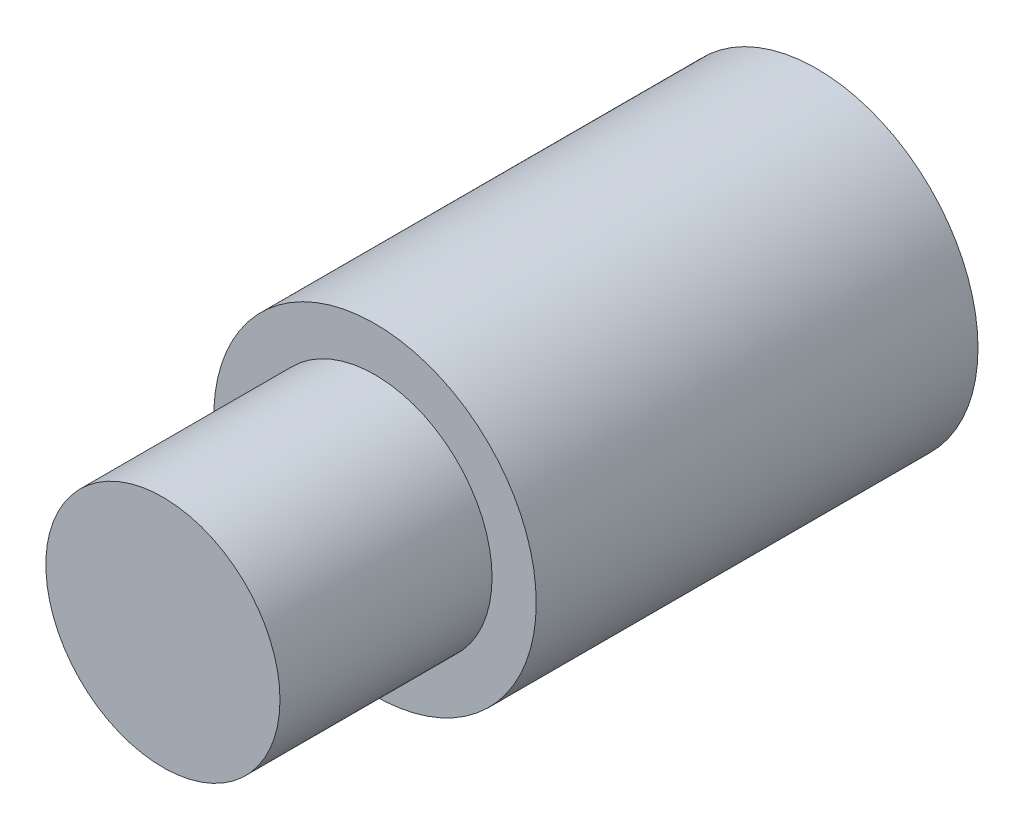
SolidWorks part; units mm, degrees
ref_plane "Front Plane" through (0, 0, 0) normal (0, 0, 1) x (1, 0, 0)
ref_plane "Top Plane" through (0, 0, 0) normal (0, 1, 0) x (1, 0, 0)
ref_plane "Right Plane" through (0, 0, 0) normal (1, 0, 0) x (0, 0, -1)
sketch "Sketch1" plane through (0, 0, 0) normal (0, 0, 1) x (1, 0, 0)
  circle A0 centre (0, 0) radius 3.65
  circle A1 centre (0, 0) radius 2.8
  dimension "D2" = 5.6
  dimension "D1" = 7.3
extrude "Boss-Extrude1" add sketch "Sketch1" along normal blind 9
sketch "Sketch2" plane through (0, 0, 9) normal (0, 0, 1) x (1, 0, 0)
  circle A0 centre (0, 0) radius 3.65 construction
  circle A1 centre (0, 0) radius 3.65
extrude "Boss-Extrude2" add sketch "Sketch2" along normal blind 1
sketch "Sketch3" plane through (0, 0, 10) normal (0, 0, 1) x (1, 0, 0)
  circle A0 centre (0, 0) radius 2.65
  dimension "D1" = 5.3
extrude "Boss-Extrude3" add sketch "Sketch3" along normal blind 4.8
equation "\"D1@Sketch1\"=5.3+2"
